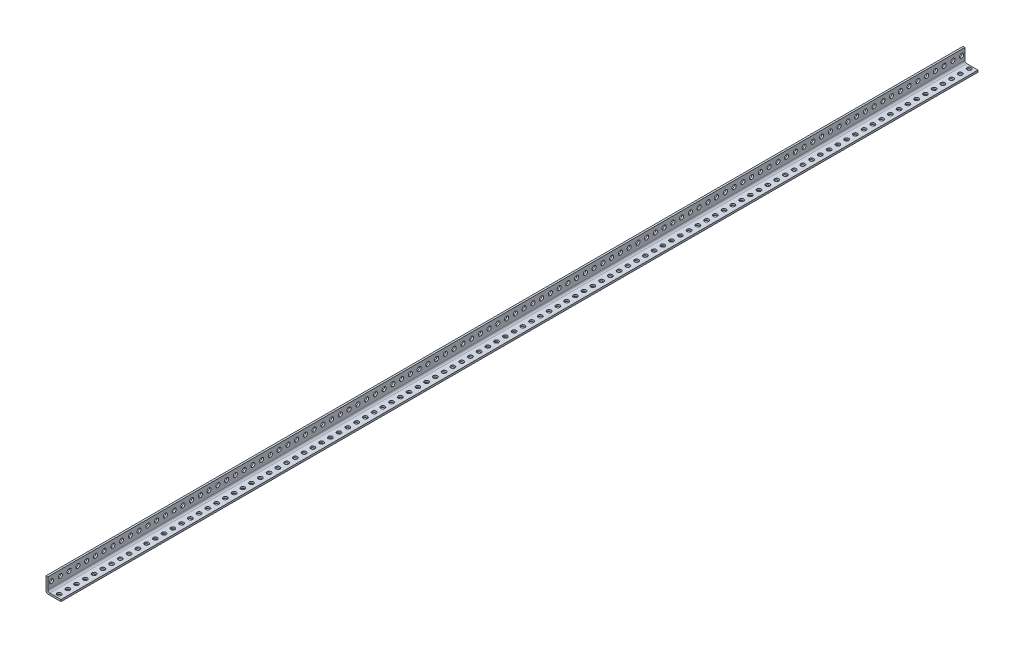
SolidWorks part; units mm, degrees
material "AISI 316 Annealed Stainless Steel Bar (SS)"
ref_plane "Front Plane" through (0, 0, 0) normal (0, 0, 1) x (1, 0, 0)
ref_plane "Top Plane" through (0, 0, 0) normal (0, 1, 0) x (1, 0, 0)
ref_plane "Right Plane" through (0, 0, 0) normal (1, 0, 0) x (0, 0, -1)
sketch "Sketch1" plane through (0, 0, 0) normal (0, 0, 1) x (1, 0, 0)
  line L0 (0, 3.175) -> (0, 25.4)
  line L1 (3.175, 0) -> (25.4, 0)
  line L2 (25.4, 0) -> (25.4, 3.175)
  line L3 (25.4, 3.175) -> (6.35, 3.175)
  line L4 (3.175, 6.35) -> (3.175, 25.4)
  line L5 (3.175, 25.4) -> (0, 25.4)
  line L6 (0, 3.175) -> (0, 0)
  line L7 (0, 0) -> (3.175, 0)
  line L8 (3.175, 6.35) -> (3.175, 3.175)
  line L9 (3.175, 3.175) -> (6.35, 3.175)
  point P11 (0, 0)
  dimension "D1" = 25.4
  dimension "D2" = 3.175
  dimension "D3" = 25.4
  dimension "D4" = 3.175
extrude "Boss-Extrude1" add sketch "Sketch1" along normal blind 1555.75
sketch "Sketch2" plane through (0, 3.175, 0) normal (0, 1, 0) x (1, 0, 0)
  circle A0 centre (15.875, -1549.4) radius 3.4925
  circle A1 centre (15.875, -1534.5552) radius 3.4925
  circle A2 centre (15.875, -1519.7104) radius 3.4925
  circle A3 centre (15.875, -1504.8657) radius 3.4925
  circle A4 centre (15.875, -1490.0209) radius 3.4925
  circle A5 centre (15.875, -1475.1761) radius 3.4925
  circle A6 centre (15.875, -1460.3313) radius 3.4925
  circle A7 centre (15.875, -1445.4866) radius 3.4925
  circle A8 centre (15.875, -1430.6418) radius 3.4925
  circle A9 centre (15.875, -1415.797) radius 3.4925
  circle A10 centre (15.875, -1400.9522) radius 3.4925
  circle A11 centre (15.875, -1386.1075) radius 3.4925
  circle A12 centre (15.875, -1371.2627) radius 3.4925
  circle A13 centre (15.875, -1356.4179) radius 3.4925
  circle A14 centre (15.875, -1341.5731) radius 3.4925
  circle A15 centre (15.875, -1326.7284) radius 3.4925
  circle A16 centre (15.875, -1311.8836) radius 3.4925
  circle A17 centre (15.875, -1297.0388) radius 3.4925
  circle A18 centre (15.875, -1282.194) radius 3.4925
  circle A19 centre (15.875, -1267.3493) radius 3.4925
  circle A20 centre (15.875, -1252.5045) radius 3.4925
  circle A21 centre (15.875, -1237.6597) radius 3.4925
  circle A22 centre (15.875, -1222.8149) radius 3.4925
  circle A23 centre (15.875, -1207.9702) radius 3.4925
  circle A24 centre (15.875, -1193.1254) radius 3.4925
  circle A25 centre (15.875, -1178.2806) radius 3.4925
  circle A26 centre (15.875, -1163.4358) radius 3.4925
  circle A27 centre (15.875, -1148.591) radius 3.4925
  circle A28 centre (15.875, -1133.7463) radius 3.4925
  circle A29 centre (15.875, -1118.9015) radius 3.4925
  circle A30 centre (15.875, -1104.0567) radius 3.4925
  circle A31 centre (15.875, -1089.2119) radius 3.4925
  circle A32 centre (15.875, -1074.3672) radius 3.4925
  circle A33 centre (15.875, -1059.5224) radius 3.4925
  circle A34 centre (15.875, -1044.6776) radius 3.4925
  circle A35 centre (15.875, -1029.8328) radius 3.4925
  circle A36 centre (15.875, -1014.9881) radius 3.4925
  circle A37 centre (15.875, -1000.1433) radius 3.4925
  circle A38 centre (15.875, -985.2985) radius 3.4925
  circle A39 centre (15.875, -970.4537) radius 3.4925
  circle A40 centre (15.875, -955.609) radius 3.4925
  circle A41 centre (15.875, -940.7642) radius 3.4925
  circle A42 centre (15.875, -925.9194) radius 3.4925
  circle A43 centre (15.875, -911.0746) radius 3.4925
  circle A44 centre (15.875, -896.2299) radius 3.4925
  circle A45 centre (15.875, -881.3851) radius 3.4925
  circle A46 centre (15.875, -866.5403) radius 3.4925
  circle A47 centre (15.875, -851.6955) radius 3.4925
  circle A48 centre (15.875, -836.8508) radius 3.4925
  circle A49 centre (15.875, -822.006) radius 3.4925
  circle A50 centre (15.875, -807.1612) radius 3.4925
  circle A51 centre (15.875, -792.3164) radius 3.4925
  circle A52 centre (15.875, -777.4716) radius 3.4925
  circle A53 centre (15.875, -762.6269) radius 3.4925
  circle A54 centre (15.875, -747.7821) radius 3.4925
  circle A55 centre (15.875, -732.9373) radius 3.4925
  circle A56 centre (15.875, -718.0925) radius 3.4925
  circle A57 centre (15.875, -703.2478) radius 3.4925
  circle A58 centre (15.875, -688.403) radius 3.4925
  circle A59 centre (15.875, -673.5582) radius 3.4925
  circle A60 centre (15.875, -658.7134) radius 3.4925
  circle A61 centre (15.875, -643.8687) radius 3.4925
  circle A62 centre (15.875, -629.0239) radius 3.4925
  circle A63 centre (15.875, -614.1791) radius 3.4925
  circle A64 centre (15.875, -599.3343) radius 3.4925
  circle A65 centre (15.875, -584.4896) radius 3.4925
  circle A66 centre (15.875, -569.6448) radius 3.4925
  circle A67 centre (15.875, -554.8) radius 3.4925
  circle A68 centre (15.875, -539.9552) radius 3.4925
  circle A69 centre (15.875, -525.1105) radius 3.4925
  circle A70 centre (15.875, -510.2657) radius 3.4925
  circle A71 centre (15.875, -495.4209) radius 3.4925
  circle A72 centre (15.875, -480.5761) radius 3.4925
  circle A73 centre (15.875, -465.7314) radius 3.4925
  circle A74 centre (15.875, -450.8866) radius 3.4925
  circle A75 centre (15.875, -436.0418) radius 3.4925
  circle A76 centre (15.875, -421.197) radius 3.4925
  circle A77 centre (15.875, -406.3522) radius 3.4925
  circle A78 centre (15.875, -391.5075) radius 3.4925
  circle A79 centre (15.875, -376.6627) radius 3.4925
  circle A80 centre (15.875, -361.8179) radius 3.4925
  circle A81 centre (15.875, -346.9731) radius 3.4925
  circle A82 centre (15.875, -332.1284) radius 3.4925
  circle A83 centre (15.875, -317.2836) radius 3.4925
  circle A84 centre (15.875, -302.4388) radius 3.4925
  circle A85 centre (15.875, -287.594) radius 3.4925
  circle A86 centre (15.875, -272.7493) radius 3.4925
  circle A87 centre (15.875, -257.9045) radius 3.4925
  circle A88 centre (15.875, -243.0597) radius 3.4925
  circle A89 centre (15.875, -228.2149) radius 3.4925
  circle A90 centre (15.875, -213.3702) radius 3.4925
  circle A91 centre (15.875, -198.5254) radius 3.4925
  circle A92 centre (15.875, -183.6806) radius 3.4925
  circle A93 centre (15.875, -168.8358) radius 3.4925
  circle A94 centre (15.875, -153.9911) radius 3.4925
  circle A95 centre (15.875, -139.1463) radius 3.4925
  circle A96 centre (15.875, -124.3015) radius 3.4925
  circle A97 centre (15.875, -109.4567) radius 3.4925
  circle A98 centre (15.875, -94.612) radius 3.4925
  circle A99 centre (15.875, -79.7672) radius 3.4925
  circle A100 centre (15.875, -64.9224) radius 3.4925
  circle A101 centre (15.875, -50.0776) radius 3.4925
  circle A102 centre (15.875, -35.2328) radius 3.4925
  circle A103 centre (15.875, -20.3881) radius 3.4925
  circle A104 centre (15.875, -5.5433) radius 3.4925
  dimension "D2" = 6.985
  dimension "D1" = 105
revolve "Cut-Revolve1" cut sketch "Sketch2" angle 360 about axis through (3.175, 3.175, 1555.75) along (0, 0, -1)
fillet "Fillet1" radius 3.175 2 edges at (3.175, 3.175, 777.875) (0, 0, 777.875)
